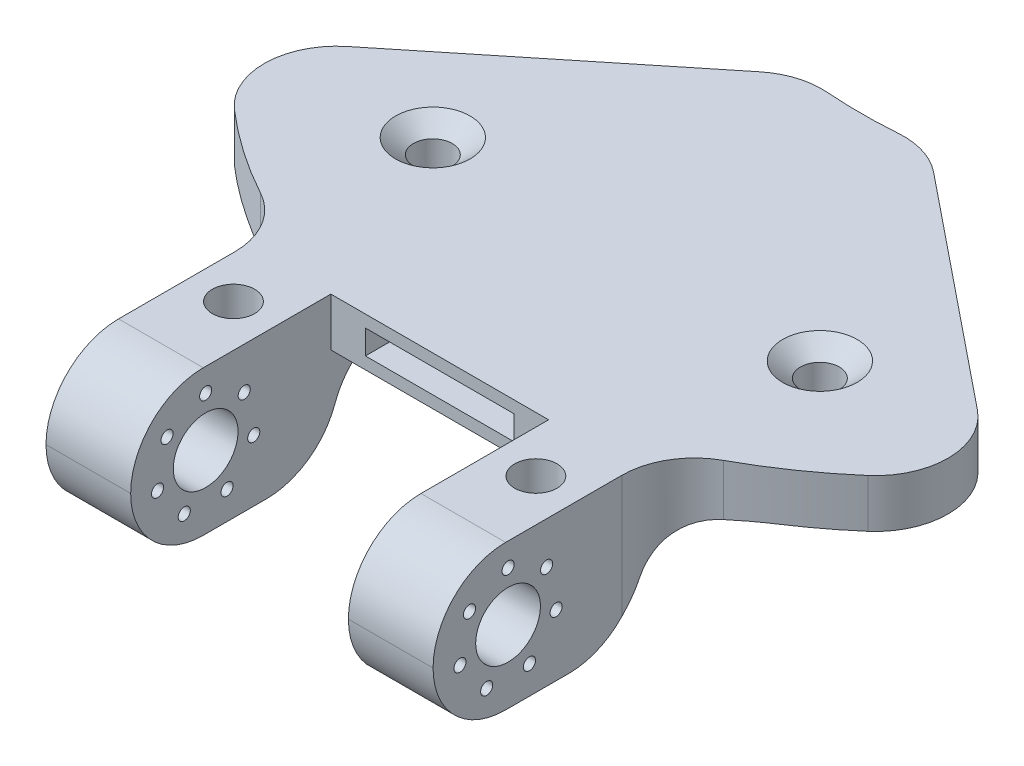
SolidWorks part; units mm, degrees
ref_plane "Front Plane" through (0, 0, 0) normal (0, 0, 1) x (1, 0, 0)
ref_plane "Top Plane" through (0, 0, 0) normal (0, 1, 0) x (1, 0, 0)
ref_plane "Right Plane" through (0, 0, 0) normal (1, 0, 0) x (0, 0, -1)
sketch "Sketch1" plane through (0, 0, 0) normal (0, 1, 0) x (1, 0, 0)
  line L0 (-41.3294, -33.3834) -> (-11.3979, -9.2065)
  line L1 (0, 0) -> (0, -63.5) construction
  line L2 (41.3294, -33.3834) -> (11.3979, -9.2065)
  line L3 (0, -63.5) -> (0, -88.9) construction
  line L4 (-25.4, -88.9) -> (-14.2875, -88.9)
  line L5 (25.4, -88.9) -> (25.4, -64.1319)
  line L6 (-25.4, -88.9) -> (-25.4, -64.1319)
  line L7 (25.4, -58.1987) -> (25.4, -60.8499) construction
  line L8 (-25.4, -58.1987) -> (-25.4, -60.8499) construction
  line L9 (-14.2875, -88.9) -> (-14.2875, -62.6241)
  line L10 (-14.2875, -68.9741) -> (14.2875, -68.9741) construction
  line L11 (14.2875, -88.9) -> (14.2875, -62.6241)
  line L12 (-14.2875, -88.9) -> (0, -88.9) construction
  line L13 (14.2875, -88.9) -> (25.4, -88.9)
  line L14 (0, -88.9) -> (14.2875, -88.9) construction
  line L15 (-14.2875, -62.6241) -> (14.2875, -62.6241)
  arc A1 (-41.5815, -47.992) -> (-30.3696, -55.7668) centre (0, 0) ccw
  arc A2 (-4.7067, -7.1174) -> (4.7067, -7.1174) centre (0, 56.2079) ccw
  arc A3 (-56.9422, 28.1039) -> (-49.3981, -39.9009) centre (0, 0) ccw construction
  arc A4 (-56.9422, 28.1039) -> (-8.3458, -6.7413) centre (0, 56.2079) ccw construction
  arc A5 (8.3458, -6.7413) -> (56.9422, 28.1039) centre (0, 56.2079) ccw construction
  arc A6 (56.9422, 28.1039) -> (-56.9422, 28.1039) centre (0, 56.2079) ccw construction
  arc A7 (49.3981, -39.9009) -> (56.9422, 28.1039) centre (0, 0) ccw construction
  arc A8 (56.9422, 28.1039) -> (-56.9422, 28.1039) centre (0, 0) ccw construction
  arc A9 (41.3294, -33.3834) -> (41.5815, -47.992) centre (35.3443, -40.7932) cw
  arc A10 (-41.3294, -33.3834) -> (-41.5815, -47.992) centre (-35.3443, -40.7932) ccw
  arc A11 (-11.3979, -9.2065) -> (-4.7067, -7.1174) centre (-5.4127, -16.6162) cw
  arc A12 (11.3979, -9.2065) -> (4.7067, -7.1174) centre (5.4127, -16.6162) ccw
  arc A13 (0, -63.5) -> (25.4, -58.1987) centre (0, 0) ccw construction
  arc A14 (30.3696, -55.7668) -> (41.5815, -47.992) centre (0, 0) ccw
  arc A15 (-25.4, -58.1987) -> (0, -63.5) centre (0, 0) ccw construction
  arc A16 (30.3696, -55.7668) -> (25.4, -64.1319) centre (34.925, -64.1319) ccw
  arc A17 (-30.3696, -55.7668) -> (-25.4, -64.1319) centre (-34.925, -64.1319) cw
  point P33 (0, -68.9741)
  dimension "D1" = 127
  dimension "D2" = 127
  dimension "D3" = 9.525
  dimension "D7" = 9.525
  dimension "D4" = 50.8
  dimension "D5" = 25.4
  dimension "D6" = 28.575
  dimension "D8" = 6.35
extrude "Boss-Extrude1" add sketch "Sketch1" along normal blind 19.05
sketch "Sketch2" plane through (-25.4, 0, 0) normal (-1, 0, 0) x (0, 0, 1)
  line L0 (88.9, 9.525) -> (79.0575, 9.525) construction
  line L1 (88.9, 19.05) -> (88.9, 0) construction
  circle A0 centre (79.0575, 9.525) radius 4.25
  dimension "D1" = 8.5
  dimension "D2" = 9.8425
extrude "Cut-Extrude1" cut sketch "Sketch2" against normal through all both and the other way through all
fillet "Fillet1" radius 9.525 4 edges at (19.8438, 0, 88.9) (-19.8437, 0, 88.9) (19.8438, 19.05, 88.9) (-19.8437, 19.05, 88.9)
sketch "Sketch3" plane through (0, 0, 0) normal (0, -1, 0) x (1, 0, 0)
  line L0 (25.5201, 62.6241) -> (-25.5201, 62.6241)
  line L1 (14.2875, 62.6241) -> (-14.2875, 62.6241)
  line L2 (-25.4, 79.375) -> (-25.4, 62.6241) construction
  line L3 (25.4, 62.6241) -> (25.4, 79.375) construction
  line L9 (25.4, 64.1319) -> (25.4, 79.375)
  line L10 (25.4, 79.375) -> (14.2875, 79.375)
  line L11 (14.2875, 79.375) -> (14.2875, 62.6241)
  line L12 (14.2875, 62.6241) -> (-14.2875, 62.6241)
  line L13 (-14.2875, 62.6241) -> (-14.2875, 79.375)
  line L14 (-14.2875, 79.375) -> (-25.4, 79.375)
  line L15 (-25.4, 79.375) -> (-25.4, 64.1319)
  line L16 (-41.3294, 33.3834) -> (-11.3979, 9.2065)
  line L17 (11.3979, 9.2065) -> (41.3294, 33.3834)
  line L18 (25.4, 64.1319) -> (25.4, 62.6241) construction
  line L19 (25.4, 79.375) -> (14.2875, 79.375) construction
  line L20 (14.2875, 79.375) -> (14.2875, 62.6241) construction
  line L22 (-14.2875, 62.6241) -> (-14.2875, 79.375) construction
  line L23 (-14.2875, 79.375) -> (-25.4, 79.375) construction
  line L24 (-25.4, 62.6241) -> (-25.4, 64.1319) construction
  line L25 (-41.3294, 33.3834) -> (-11.3979, 9.2065)
  line L26 (11.3979, 9.2065) -> (41.3294, 33.3834)
  arc A0 (-25.5201, 62.6241) -> (-25.4, 64.1319) centre (-34.925, 64.1319) ccw construction
  arc A1 (25.4, 64.1319) -> (25.5201, 62.6241) centre (34.925, 64.1319) ccw construction
  arc A9 (-30.3696, 55.7668) -> (-25.4, 64.1319) centre (-34.925, 64.1319) ccw
  arc A10 (-30.3696, 55.7668) -> (-41.5815, 47.992) centre (0, 0) ccw
  arc A11 (-41.5815, 47.992) -> (-41.3294, 33.3834) centre (-35.3443, 40.7932) ccw
  arc A12 (-11.3979, 9.2065) -> (-4.7067, 7.1174) centre (-5.4127, 16.6162) ccw
  arc A13 (4.7067, 7.1174) -> (-4.7067, 7.1174) centre (0, -56.2079) ccw
  arc A14 (4.7067, 7.1174) -> (11.3979, 9.2065) centre (5.4127, 16.6162) ccw
  arc A15 (41.3294, 33.3834) -> (41.5815, 47.992) centre (35.3443, 40.7932) ccw
  arc A16 (41.5815, 47.992) -> (30.3696, 55.7668) centre (0, 0) ccw
  arc A17 (25.4, 64.1319) -> (30.3696, 55.7668) centre (34.925, 64.1319) ccw
  arc A18 (-30.3696, 55.7668) -> (-25.5201, 62.6241) centre (-34.925, 64.1319) ccw
  arc A19 (-30.3696, 55.7668) -> (-41.5815, 47.992) centre (0, 0) ccw
  arc A20 (-41.5815, 47.992) -> (-41.3294, 33.3834) centre (-35.3443, 40.7932) ccw
  arc A21 (-11.3979, 9.2065) -> (-4.7067, 7.1174) centre (-5.4127, 16.6162) ccw
  arc A22 (4.7067, 7.1174) -> (-4.7067, 7.1174) centre (0, -56.2079) ccw
  arc A23 (4.7067, 7.1174) -> (11.3979, 9.2065) centre (5.4127, 16.6162) ccw
  arc A24 (41.3294, 33.3834) -> (41.5815, 47.992) centre (35.3443, 40.7932) ccw
  arc A25 (41.5815, 47.992) -> (30.3696, 55.7668) centre (0, 0) ccw
  arc A26 (25.5201, 62.6241) -> (30.3696, 55.7668) centre (34.925, 64.1319) ccw
  point P25 (0, 0)
  arc M26 (-25.4, 64.1319) -> (-30.3696, 55.7668) centre (-34.925, 64.1319) cw
  arc M27 (-30.3696, 55.7668) -> (-41.5815, 47.992) centre (0, 0) ccw
  arc M28 (-41.5815, 47.992) -> (-41.3294, 33.3834) centre (-35.3443, 40.7932) ccw
  line M29 (-41.3294, 33.3834) -> (-11.3979, 9.2065)
  arc M30 (-11.3979, 9.2065) -> (-4.7067, 7.1174) centre (-5.4127, 16.6162) ccw
  arc M31 (-4.7067, 7.1174) -> (4.7067, 7.1174) centre (0, -56.2079) cw
  arc M32 (4.7067, 7.1174) -> (11.3979, 9.2065) centre (5.4127, 16.6162) ccw
  line M33 (11.3979, 9.2065) -> (41.3294, 33.3834)
  arc M34 (41.3294, 33.3834) -> (41.5815, 47.992) centre (35.3443, 40.7932) ccw
  arc M35 (41.5815, 47.992) -> (30.3696, 55.7668) centre (0, 0) ccw
  arc M36 (30.3696, 55.7668) -> (25.4, 64.1319) centre (34.925, 64.1319) cw
  line M38 (14.2875, 62.6241) -> (-14.2875, 62.6241)
  dimension "D1" = 0
extrude "Cut-Extrude2" cut sketch "Sketch3" against normal offset from surface (12.7 mm away) 6.35 contours L0 M36 M38 M26 M27 M28 M29 M30 M31 M32 M33 M34 M35 region at (0, 0, 37.8623) up to face at (0, 19.05, 48.6647)
fillet "Fillet2" radius 9.525 2 edges at (19.9038, 12.7, 62.6241) (-19.9038, 12.7, 62.6241)
fillet "Fillet3" radius 9.525 2 edges at (-19.9038, 0, 62.6241) (19.9038, 0, 62.6241)
hole_wizard "PlateMount - CSK for #10 Flat Head Machine Screw (100)2" positions "Sketch4" profile "Sketch5" countersink size "#10" standard "ANSI Inch" end condition up to next
sketch "Sketch4" plane through (0, 19.05, 0) normal (0, 1, 0) x (1, 0, 0)
  line L0 (0, -68.9741) -> (0, -7.2921) construction
  line L2 (-25.4, -38.1331) -> (25.4, -38.1331) construction
  arc A0 (-4.7067, -7.1174) -> (4.7067, -7.1174) centre (0, 56.2079) ccw construction
  point P12 (25.4, -38.1331)
  point P14 (-25.4, -38.1331)
  point P23 (0, 0)
  dimension "D1" = 50.8
sketch "Sketch5" plane through (-25.4, 19.05, 38.1331) normal (1, 0, 0) x (0, 0, 1)
  line L0 (0, 0) -> (0, 6.35)
  line L1 (0, 6.35) -> (2.5527, 6.35)
  line L2 (2.5527, 6.35) -> (2.5527, 1.9608)
  line L3 (2.5527, 1.9608) -> (4.8895, 0)
  line L5 (4.8895, 0) -> (0, 0)
  line L6 (-2.5527, 1.9608) -> (-4.8895, 0) construction
  line L11 (0, -6.35) -> (0, 107.95) construction
  dimension "Thru Hole Dia." = 5.1054
  dimension "Thru Hole Depth" = 6.35
  dimension "Near C'Sink Dia." = 9.779
  dimension "Near C'Sink Angle" = 100
sketch "Sketch6" plane through (0, 0, 0) normal (0, -1, 0) x (1, 0, 0)
  line L0 (-19.8437, 79.375) -> (-19.8437, 69.85) construction
  line L1 (-14.2875, 79.375) -> (-25.4, 79.375) construction
  line L2 (-19.8437, 79.375) -> (19.8438, 79.375) construction
  line L3 (25.4, 79.375) -> (14.2875, 79.375) construction
  line L4 (0, 79.375) -> (0, 50.9244) construction
  circle A0 centre (-19.8437, 69.85) radius 2.7781
  circle A1 centre (19.8437, 69.85) radius 2.7781
  dimension "D2" = 5.5562
  dimension "D1" = 9.525
extrude "MagnetPilotHoles" cut sketch "Sketch6" against normal through all both and the other way through all
sketch "Sketch7" plane through (-25.4, 0, 0) normal (-1, 0, 0) x (0, 0, 1)
  circle A1 centre (79.0575, 15.9975) radius 0.7937
  circle A2 centre (79.0575, 9.525) radius 6.4725
  circle A3 centre (79.0575, 9.525) radius 6.4725 construction
  circle A4 centre (84.1179, 13.5605) radius 0.7937
  circle A5 centre (85.3677, 8.0847) radius 0.7937
  circle A6 centre (81.8658, 3.6935) radius 0.7937
  circle A7 centre (76.2492, 3.6935) radius 0.7937
  circle A8 centre (72.7473, 8.0847) radius 0.7937
  circle A9 centre (73.9971, 13.5605) radius 0.7937
  point P19 (79.0575, 9.525)
  dimension "D2" = 1.5875
  dimension "D1" = 2.2225
  dimension "D3" = 7
extrude "ConcentricSpring" cut sketch "Sketch7" against normal through all
sketch "Sketch8" plane through (0, 0, 62.6241) normal (0, 0, 1) x (1, 0, 0)
  line L0 (0, 19.05) -> (0, 15.875) construction
  line L1 (-14.2875, 19.05) -> (14.2875, 19.05) construction
  line L3 (-9.7531, 17.4625) -> (9.7531, 17.4625)
  line L4 (-9.7531, 17.4625) -> (-9.7531, 14.2875)
  line L5 (-9.7531, 14.2875) -> (9.7531, 14.2875)
  line L6 (9.7531, 17.4625) -> (9.7531, 14.2875)
  line L7 (-9.7531, 17.4625) -> (9.7531, 14.2875) construction
  line L8 (-9.7531, 14.2875) -> (9.7531, 17.4625) construction
  dimension "D1" = 3.175
  dimension "D2" = 3.175
extrude "FlatSpring" cut sketch "Sketch8" against normal blind 12.7
